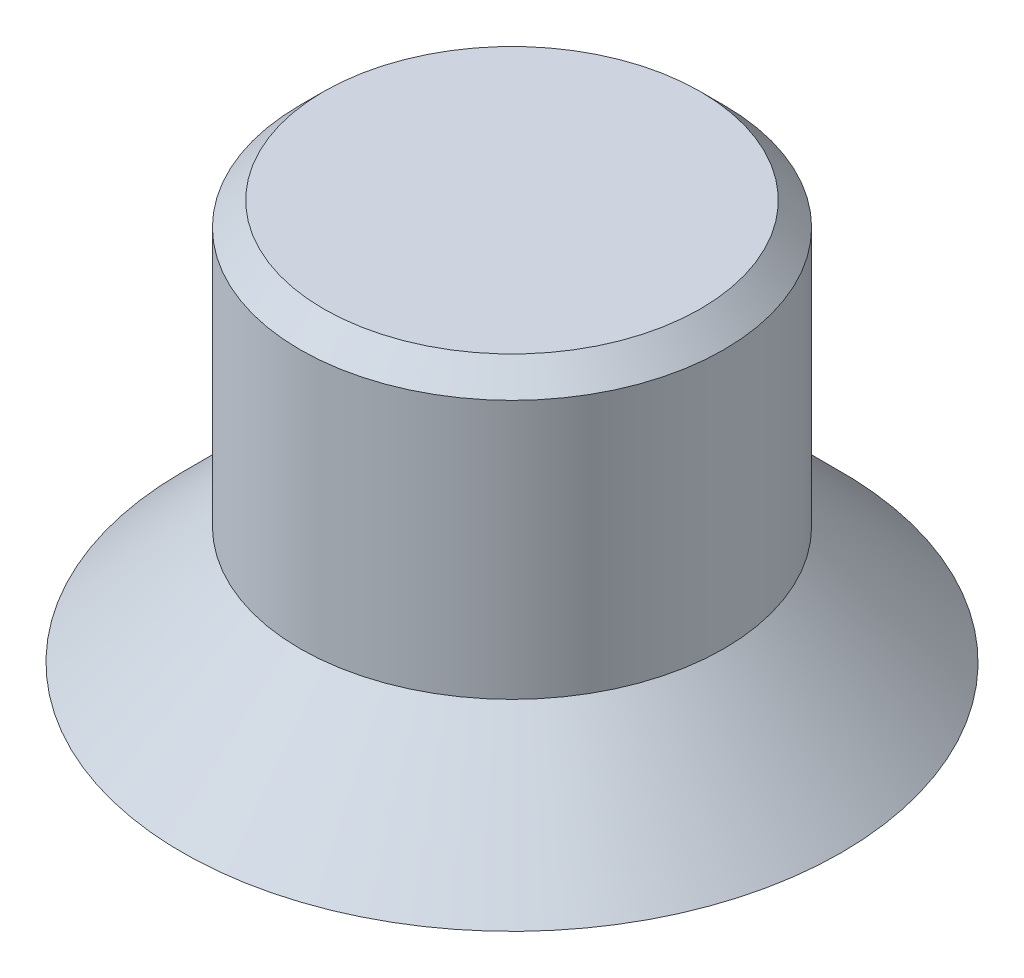
SolidWorks part; units mm, degrees
ref_plane "Front Plane" through (0, 0, 0) normal (0, 0, 1) x (1, 0, 0)
ref_plane "Top Plane" through (0, 0, 0) normal (0, 1, 0) x (1, 0, 0)
ref_plane "Right Plane" through (0, 0, 0) normal (1, 0, 0) x (0, 0, -1)
sketch "Sketch1" plane through (0, 0, 0) normal (0, 0, 1) x (1, 0, 0)
  line L0 (0, 1) -> (1.5, 1)
  line L1 (1.5, 1) -> (1.6763, 0)
  line L2 (1.6763, 0) -> (3.5, 0)
  line L3 (3.5, 0) -> (2.25, 1.25)
  line L4 (2.25, 1.25) -> (2.25, 4.25)
  line L5 (2.25, 4.25) -> (0, 4.25)
  line L6 (0, 4.25) -> (0, 1)
  line L7 (0, -277.7981) -> (0, 13612.105) construction
  dimension "D1" = 1.5
  dimension "D2" = 100
  dimension "D3" = 45
  dimension "D4" = 2.25
  dimension "D5" = 1
  dimension "D6" = 3
  dimension "D7" = 3.5
revolve "Revolve1" add sketch "Sketch1" angle 360 about L7
chamfer "Chamfer1" distance 0.25 angle 45 1 edges at (2.25, 4.25, 0)
